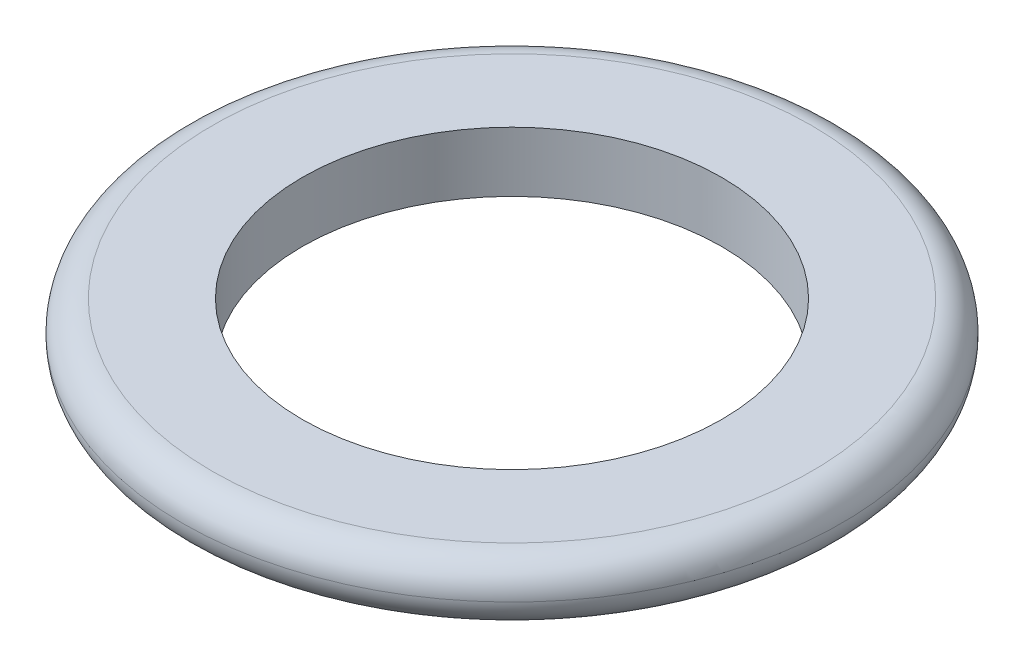
SolidWorks part; units mm, degrees
material "AISI 304"
ref_plane "Front" through (0, 0, 0) normal (0, 0, 1) x (1, 0, 0)
ref_plane "Top" through (0, 0, 0) normal (0, 1, 0) x (1, 0, 0)
ref_plane "Right" through (0, 0, 0) normal (1, 0, 0) x (0, 0, -1)
sketch "草图1" plane through (0, 0, 0) normal (0, 1, 0) x (1, 0, 0)
  circle A0 centre (0, 0) radius 3.5
  circle A1 centre (0, 0) radius 5.5
  dimension "垫圈内径" = 7
  dimension "垫圈外径" = 11
extrude "凸台-拉伸1" add sketch "草图1" along normal mid plane 1
fillet "圆角1" radius 0.5 2 edges at (0, -0.5, 5.5) (0, 0.5, 5.5)
